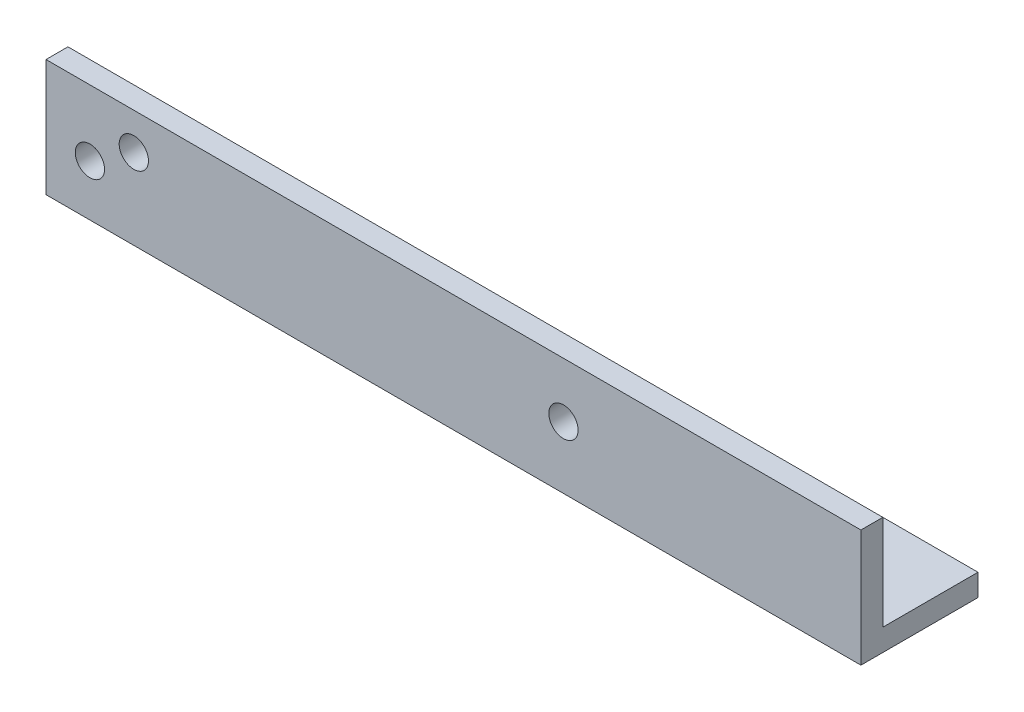
SolidWorks part; units mm, degrees
material "6061 Alloy"
ref_plane "Front Plane" through (0, 0, 0) normal (0, 0, 1) x (1, 0, 0)
ref_plane "Top Plane" through (0, 0, 0) normal (0, 1, 0) x (1, 0, 0)
ref_plane "Right Plane" through (0, 0, 0) normal (1, 0, 0) x (0, 0, -1)
sketch "Sketch1" plane through (0, 0, 0) normal (1, 0, 0) x (0, 0, -1)
  line L0 (0, 0) -> (0, -25.4)
  line L1 (0, -25.4) -> (25.4, -25.4)
  line L2 (25.4, -25.4) -> (25.4, -20.6375)
  line L3 (25.4, -20.6375) -> (4.7625, -20.6375)
  line L4 (4.7625, -20.6375) -> (4.7625, 0)
  line L5 (4.7625, 0) -> (0, 0)
  dimension "D1" = 4.7625
  dimension "D2" = 4.7625
  dimension "D3" = 25.4
  dimension "D4" = 25.4
extrude "Boss-Extrude1" add sketch "Sketch1" along normal blind 176.784
sketch "Sketch3" plane through (0, 0, -4.7625) normal (0, 0, -1) x (-1, 0, 0)
  line L0 (0, -20.6375) -> (0, 0) construction
  line L1 (-176.784, -25.4) -> (0, -25.4) construction
  circle A0 centre (-9.525, -14.2875) radius 3.175
  circle A1 centre (-19.05, -7.9375) radius 3.175
  dimension "D1" = 6.35
  dimension "D2" = 6.35
  dimension "D3" = 9.525
  dimension "D4" = 19.05
  dimension "D5" = 11.1125
  dimension "D6" = 17.4625
extrude "Cut-Extrude1" cut sketch "Sketch3" against normal up to next
sketch "Sketch4" plane through (0, 0, 0) normal (0, 0, 1) x (1, 0, 0)
  circle A1 centre (112.2532, -11.9296) radius 3.175
  circle A2 centre (112.2532, -11.9296) radius 3.175 construction
extrude "Cut-Extrude2" cut sketch "Sketch4" against normal up to next
sketch "Sketch5" plane through (0, -25.4, 0) normal (0, -1, 0) x (1, 0, 0)
  circle A0 centre (138.684, -12.7) radius 3.175 construction
  circle A1 centre (157.734, -12.7) radius 3.175 construction
  circle A2 centre (138.684, -12.7) radius 3.175
  circle A3 centre (157.734, -12.7) radius 3.175
extrude "Cut-Extrude4" cut sketch "Sketch5" against normal up to next
